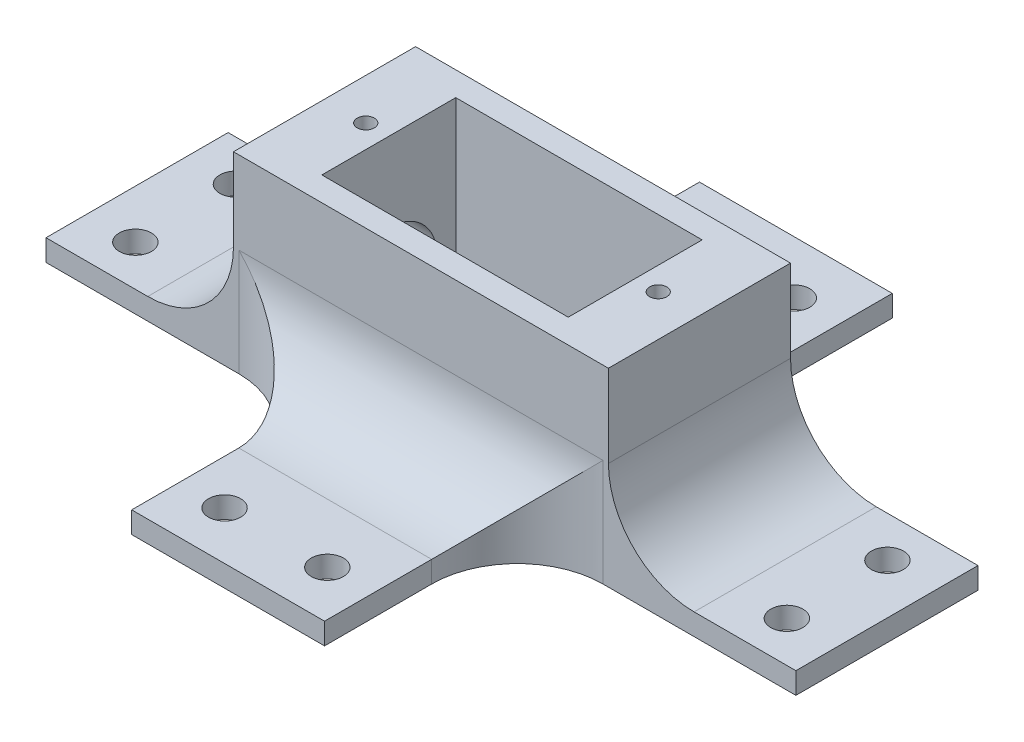
SolidWorks part; units mm, degrees
material "ABS"
ref_plane "Front Plane" through (0, 0, 0) normal (0, 0, 1) x (1, 0, 0)
ref_plane "Top Plane" through (0, 0, 0) normal (0, 1, 0) x (1, 0, 0)
ref_plane "Right Plane" through (0, 0, 0) normal (1, 0, 0) x (0, 0, -1)
sketch "Sketch2" plane through (0, 0, 0) normal (0, 1, 0) x (1, 0, 0)
  line L1 (-35, -8.5) -> (35, -8.5)
  line L2 (-35, -8.5) -> (-35, 8.5)
  line L3 (-35, 8.5) -> (35, 8.5)
  line L4 (35, -8.5) -> (35, 8.5)
  line L5 (-35, -8.5) -> (35, 8.5) construction
  line L6 (-35, 8.5) -> (35, -8.5) construction
  point P0 (0, 0)
  dimension "D1" = 17
  dimension "D2" = 70
extrude "Boss-Extrude1" add sketch "Sketch2" along normal blind 2
sketch "Sketch3" plane through (0, 2, 0) normal (0, 1, 0) x (1, 0, 0)
  line L0 (35, 8.5) -> (-35, 8.5) construction
  line L1 (-17.5, -8.5) -> (17.5, -8.5)
  line L2 (-17.5, -8.5) -> (-17.5, 8.5)
  line L3 (-17.5, 8.5) -> (17.5, 8.5)
  line L4 (17.5, -8.5) -> (17.5, 8.5)
  line L5 (-17.5, -8.5) -> (17.5, 8.5) construction
  line L6 (-17.5, 8.5) -> (17.5, -8.5) construction
  point P0 (0, 0)
  dimension "D1" = 35
extrude "Boss-Extrude2" add sketch "Sketch3" along normal blind 15.7
sketch "Sketch4" plane through (0, 17.7, 0) normal (0, 1, 0) x (1, 0, 0)
  line L1 (-11.5, -6.25) -> (11.5, -6.25)
  line L2 (-11.5, -6.25) -> (-11.5, 6.25)
  line L3 (-11.5, 6.25) -> (11.5, 6.25)
  line L4 (11.5, -6.25) -> (11.5, 6.25)
  line L5 (-11.5, -6.25) -> (11.5, 6.25) construction
  line L6 (-11.5, 6.25) -> (11.5, -6.25) construction
  point P0 (0, 0)
  dimension "D1" = 23
  dimension "D2" = 12.5
extrude "Cut-Extrude1" cut sketch "Sketch4" against normal through all
sketch "Sketch6" plane through (0, 17.7, 0) normal (0, 1, 0) x (1, 0, 0)
  line L0 (0, -1.1) -> (0, 1.1) construction
  circle A0 centre (13.65, 0) radius 0.8
  circle A1 centre (-13.65, 0) radius 0.8
  dimension "D1" = 27.3
extrude "Cut-Extrude2" cut sketch "Sketch6" against normal blind 8
sketch "Sketch7" plane through (-17.5, 0, 0) normal (-1, 0, 0) x (0, 0, 1)
  line L0 (0, -9.735) -> (0, 9.735) construction
  line L2 (-4.5, 5.8) -> (-4.5, 3.8)
  line L3 (-4.5, 3.8) -> (4.5, 3.8)
  line L4 (4.5, 5.8) -> (4.5, 3.8)
  line L5 (-4.5, 5.8) -> (4.5, 3.8) construction
  line L6 (-4.5, 3.8) -> (4.5, 5.8) construction
  line L7 (9.35, 0) -> (-9.35, 0) construction
  arc A0 (-4.5, 5.8) -> (4.5, 5.8) centre (0, 5.8) cw
  point P0 (0, 4.8)
  dimension "D1" = 9
  dimension "D2" = 2
  dimension "D3" = 3.8
extrude "Cut-Extrude3" cut sketch "Sketch7" against normal blind 8
sketch "Sketch9" plane through (0, 0, 8.5) normal (0, 0, 1) x (1, 0, 0)
  line L0 (0, -9.35) -> (0, 9.35) construction
  line L1 (-9, 2) -> (9, 2)
  line L2 (-9, 2) -> (-9, 0)
  line L3 (-9, 0) -> (9, 0)
  line L4 (9, 2) -> (9, 0)
  line L5 (-9, 2) -> (9, 0) construction
  line L6 (-9, 0) -> (9, 2) construction
  line L7 (9.35, 0) -> (-9.35, 0) construction
  line L8 (-35, 2) -> (-17.5, 2) construction
  point P0 (0, 1)
  dimension "D1" = 18
extrude "Boss-Extrude3" add sketch "Sketch9" along normal blind 18
mirror "Mirror1" about plane through (0, 0, 0) normal (0, 0, 1) of "Boss-Extrude3"
fillet "Fillet1" radius 8 1 edges at (0, 2, 8.5)
fillet "Fillet2" radius 8 6 edges at (-9, 1, -8.5) (-9, 5, 8.5) (9, 5, 8.5) (9, 1, -8.5) (0, 2, -8.5) (17.5, 2, 0)
fillet "Fillet3" radius 8 1 edges at (-17.5, 2, 0)
sketch "Sketch11" plane through (0, 2, 0) normal (0, 1, 0) x (1, 0, 0)
  circle A0 centre (4.7727, 21.5294) radius 1.5
  circle A1 centre (-4.8211, 21.5294) radius 1.5
  circle A2 centre (4.7727, -22.011) radius 1.5
  circle A3 centre (-4.8211, -22.011) radius 1.5
  circle A4 centre (30.3487, 4.6963) radius 1.5
  circle A5 centre (30.3487, -4.6912) radius 1.5
  circle A6 centre (-30.4672, -4.6912) radius 1.5
  circle A7 centre (-30.4672, 4.6963) radius 1.5
extrude "Cut-Extrude4" cut sketch "Sketch11" against normal blind 18
